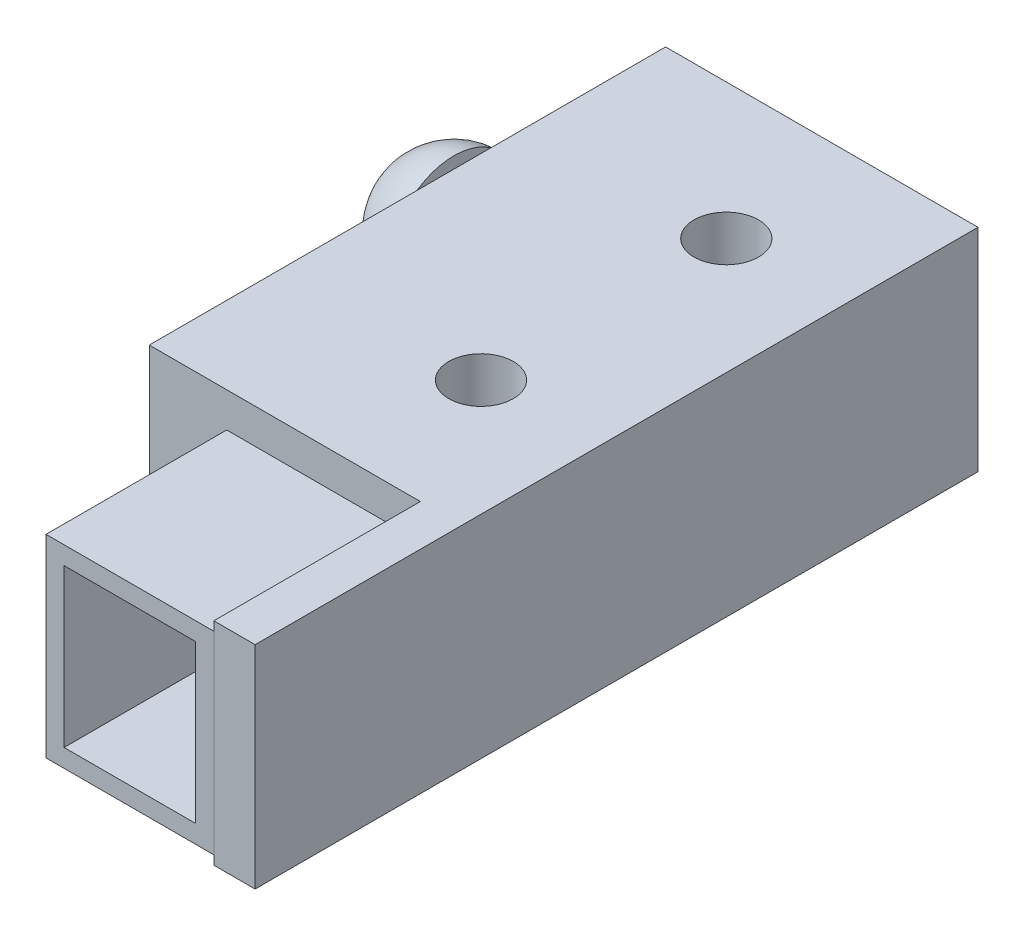
SolidWorks part; units mm, degrees
ref_plane "前视基准面" through (0, 0, 0) normal (0, 0, 1) x (1, 0, 0)
ref_plane "上视基准面" through (0, 0, 0) normal (0, 1, 0) x (1, 0, 0)
ref_plane "右视基准面" through (0, 0, 0) normal (1, 0, 0) x (0, 0, -1)
sketch "草图1" plane through (0, 0, 0) normal (0, 1, 0) x (1, 0, 0)
  line L0 (-39.6021, 0) -> (48.2381, 0) construction
  line L1 (0, 37.6899) -> (0, -38.1834) construction
  line L2 (-7.6, 10) -> (2.9, 10)
  line L3 (2.9, 10) -> (2.9, -10)
  line L4 (2.9, -10) -> (-7.6, -10)
  line L5 (-7.6, -10) -> (-7.6, 10)
  circle A0 centre (0, 4.75) radius 1.25
  circle A1 centre (0, -4.75) radius 1.25
  dimension "D1" = 2.5
  dimension "D2" = 9.5
  dimension "D3" = 20
  dimension "D4" = 2.9
  dimension "D5" = 10.5
extrude "凸台-拉伸1" add sketch "草图1" along normal blind 6.5
sketch "草图2" plane through (-7.6, 0, 0) normal (-1, 0, 0) x (0, 0, 1)
  line L0 (-18.8851, 3.25) -> (29.668, 3.25) construction
  line L1 (-10, 0) -> (10, 0) construction
  line L2 (-10, 6.5) -> (10, 6.5) construction
  line L3 (-10, 6.5) -> (-10, 0) construction
  line L4 (-4, 1.5) -> (-2, 1.5)
  line L5 (-4, 1.5) -> (-4, 5)
  line L6 (-4, 5) -> (-2, 5)
  line L7 (-2, 1.5) -> (-2, 5)
  line L8 (-4, 1.5) -> (-2, 5) construction
  line L9 (-4, 5) -> (-2, 1.5) construction
  point P6 (-3, 3.25)
  dimension "D1" = 3.5
  dimension "D2" = 6
  dimension "D3" = 2
extrude "凸台-拉伸2" add sketch "草图2" along normal blind 1.2
sketch "草图3" plane through (-8.8, 0, 0) normal (-1, 0, 0) x (0, 0, 1)
  circle A0 centre (-3, 3.25) radius 2.5
  point P2 (0, 0)
  dimension "D1" = 5
extrude "凸台-拉伸3" add sketch "草图3" along normal blind 2.5
fillet "圆角1" radius 2.5 1 edges at (-11.3, 3.25, -0.5)
sketch "草图4" plane through (2.9, 0, 0) normal (1, 0, 0) x (0, 0, -1)
  line L0 (10, 6.5) -> (-18, 6.5)
  line L1 (-18, 6.5) -> (-18, -1.7)
  line L2 (-18, -1.7) -> (10, -1.7)
  line L3 (10, -1.7) -> (10, 6.5)
  point P6 (0, 0)
  dimension "D1" = 8.2
  dimension "D2" = 28
extrude "凸台-拉伸4" add sketch "草图4" along normal blind 1.6
sketch "草图5" plane through (2.9, 0, 0) normal (-1, 0, 0) x (0, 0, 1)
  line L0 (11, -1.35) -> (11, 6.15)
  line L1 (11, 6.15) -> (18, 6.15)
  line L2 (18, 6.5) -> (18, -1.7) construction
  line L3 (18, 6.15) -> (18, -1.35)
  line L4 (18, -1.35) -> (11, -1.35)
  line L5 (18, -1.7) -> (-10, -1.7) construction
  dimension "D1" = 7
  dimension "D2" = 7.5
  dimension "D3" = 0.35
extrude "凸台-拉伸5" add sketch "草图5" along normal blind 6.5 separate body
shell "抽壳1" thickness 0.7 removed face at (-0.35, 2.4, 18)
